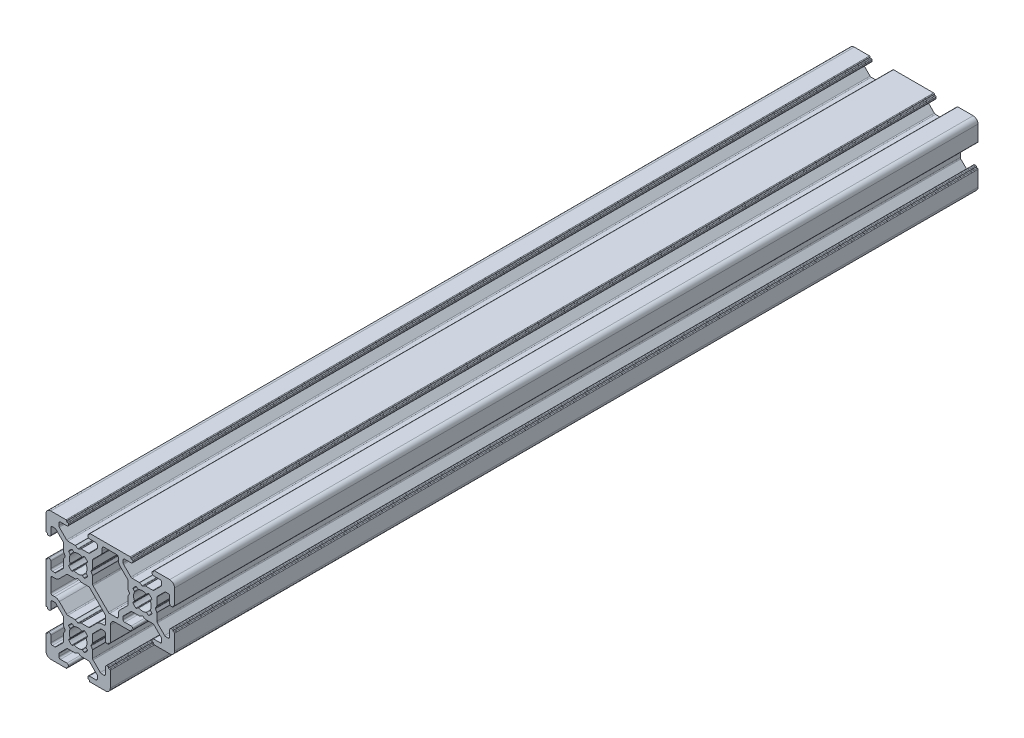
SolidWorks part; units mm, degrees
ref_plane "Front Plane" through (0, 0, 0) normal (0, 0, 1) x (1, 0, 0)
ref_plane "Top Plane" through (0, 0, 0) normal (0, 1, 0) x (1, 0, 0)
ref_plane "Right Plane" through (0, 0, 0) normal (1, 0, 0) x (0, 0, -1)
sketch "Sketch1" plane through (0, 0, 0) normal (0, 0, 1) x (1, 0, 0)
  line L0 (-3.2322, -4.5) -> (-0.9536, -4.5)
  line L1 (-0.8536, -4.4732) -> (-0.1, -4.0381)
  line L2 (0.1, -4.0381) -> (0.8536, -4.4732)
  line L3 (0.9536, -4.5) -> (3.2322, -4.5)
  line L4 (3.5858, -4.6464) -> (8.3536, -9.4142)
  line L5 (8.5, -12) -> (8.5, -9.7678)
  line L6 (-3.55, 9.7) -> (-3.55, 9.8)
  line L7 (-3.35, 9.5) -> (-3.2, 9.5)
  line L8 (-3, 9) -> (-3, 9.3)
  line L9 (-5.5, 8.5) -> (-3.5, 8.5)
  line L10 (-6, 7.2678) -> (-6, 8)
  line L12 (-3.2322, 4.5) -> (-0.9536, 4.5)
  line L13 (-0.8536, 4.4732) -> (-0.1, 4.0381)
  line L14 (0.1, 4.0381) -> (0.8536, 4.4732)
  line L15 (0.9536, 4.5) -> (3.2322, 4.5)
  line L16 (3.5858, 4.6464) -> (5.8536, 6.9142)
  line L17 (6, 7.2678) -> (6, 8)
  line L18 (5.5, 8.5) -> (3.5, 8.5)
  line L19 (3, 9) -> (3, 9.3)
  line L20 (3.2, 9.5) -> (3.3, 9.5)
  line L21 (3.5, 9.7) -> (3.5, 9.8)
  line L23 (3.7, 10) -> (16.2, 10)
  line L24 (16.4, 9.7) -> (16.4, 9.8)
  line L25 (16.6, 9.5) -> (16.8, 9.5)
  line L26 (17, 9) -> (17, 9.3)
  line L27 (14.5, 8.5) -> (16.5, 8.5)
  line L28 (14, 7.2678) -> (14, 8)
  line L29 (14.1464, 6.9142) -> (16.4142, 4.6464)
  line L30 (16.7678, 4.5) -> (19.0464, 4.5)
  line L31 (19.1464, 4.4732) -> (19.9, 4.0381)
  line L32 (20.1, 4.0381) -> (20.8536, 4.4732)
  line L33 (20.9536, 4.5) -> (23.2322, 4.5)
  line L34 (23.5858, 4.6464) -> (25.8536, 6.9142)
  line L35 (26, 7.2678) -> (26, 8)
  line L36 (25.5, 8.5) -> (23.5, 8.5)
  line L37 (23, 9) -> (23, 9.3)
  line L38 (23.2, 9.5) -> (23.3, 9.5)
  line L39 (23.5, 9.7) -> (23.5, 9.8)
  line L40 (23.7, 10) -> (28.5, 10)
  line L41 (30, 3.7) -> (30, 8.5)
  line L42 (29.7, 3.5) -> (29.8, 3.5)
  line L43 (29.5, 3.2) -> (29.5, 3.3)
  line L44 (29, 3) -> (29.3, 3)
  line L45 (28.5, 3.5) -> (28.5, 5.5)
  line L46 (27.2678, 6) -> (28, 6)
  line L47 (24.6464, 3.5858) -> (26.9142, 5.8536)
  line L48 (24.5, 0.9536) -> (24.5, 3.2322)
  line L49 (24.0381, 0.1) -> (24.4732, 0.8536)
  line L50 (24.0381, -0.1) -> (24.4732, -0.8536)
  line L51 (24.5, -3.2322) -> (24.5, -0.9536)
  line L52 (24.6464, -3.5858) -> (26.9142, -5.8536)
  line L53 (27.2678, -6) -> (28, -6)
  line L54 (28.5, -5.5) -> (28.5, -3.5)
  line L55 (29, -3) -> (29.3, -3)
  line L56 (29.5, -3.3) -> (29.5, -3.2)
  line L57 (29.7, -3.5) -> (29.8, -3.5)
  line L58 (30, -8.5) -> (30, -3.7)
  line L59 (23.7, -10) -> (28.5, -10)
  line L60 (23.5, -9.8) -> (23.5, -9.7)
  line L61 (23.2, -9.5) -> (23.3, -9.5)
  line L62 (23, -9.3) -> (23, -9)
  line L63 (23.5, -8.5) -> (25.5, -8.5)
  line L64 (26, -8) -> (26, -7.2678)
  line L65 (25.8536, -6.9142) -> (23.5858, -4.6464)
  line L66 (23.2322, -4.5) -> (20.9536, -4.5)
  line L67 (20.8536, -4.4732) -> (20.1, -4.0381)
  line L68 (19.1464, -4.4732) -> (19.9, -4.0381)
  line L69 (19.0464, -4.5) -> (16.7678, -4.5)
  line L70 (14.1464, -6.9142) -> (16.4142, -4.6464)
  line L71 (14, -8) -> (14, -7.2678)
  line L72 (14.5, -8.5) -> (16.5, -8.5)
  line L73 (17, -9.3) -> (17, -9)
  line L74 (16.65, -9.5) -> (16.8, -9.5)
  line L75 (16.45, -9.8) -> (16.45, -9.7)
  line L76 (11.5, -10) -> (16.25, -10)
  line L77 (10, -16.3) -> (10, -11.5)
  line L78 (9.8, -16.5) -> (9.7, -16.5)
  line L79 (9.5, -16.8) -> (9.5, -16.7)
  line L80 (9.3, -17) -> (9, -17)
  line L81 (8.5, -16.5) -> (8.5, -14.5)
  line L82 (7.2678, -14) -> (8, -14)
  line L83 (4.6464, -16.4142) -> (6.9142, -14.1464)
  line L84 (4.5, -19.0464) -> (4.5, -16.7678)
  line L85 (4.0381, -19.9) -> (4.4732, -19.1464)
  line L86 (4.0381, -20.1) -> (4.4732, -20.8536)
  line L87 (4.5, -23.2322) -> (4.5, -20.9536)
  line L88 (4.6464, -23.5858) -> (6.9142, -25.8536)
  line L89 (7.2678, -26) -> (8, -26)
  line L90 (8.5, -25.5) -> (8.5, -23.5)
  line L91 (9, -23) -> (9.3, -23)
  line L92 (9.5, -23.3) -> (9.5, -23.2)
  line L93 (9.7, -23.5) -> (9.8, -23.5)
  line L94 (10, -28.5) -> (10, -23.7)
  line L95 (8.5, -30) -> (3.7, -30)
  line L96 (3.5, -29.8) -> (3.5, -29.7)
  line L97 (3.3, -29.5) -> (3.2, -29.5)
  line L98 (3, -29.3) -> (3, -29)
  line L99 (3.5, -28.5) -> (5.5, -28.5)
  line L100 (6, -28) -> (6, -27.2678)
  line L101 (5.8536, -26.9142) -> (3.5858, -24.6464)
  line L102 (3.2322, -24.5) -> (0.9536, -24.5)
  line L103 (0.8536, -24.4732) -> (0.1, -24.0381)
  line L104 (-0.8536, -24.4732) -> (-0.1, -24.0381)
  line L105 (-0.9536, -24.5) -> (-3.2322, -24.5)
  line L106 (-5.8536, -26.9142) -> (-3.5858, -24.6464)
  line L107 (-6, -28) -> (-6, -27.2678)
  line L108 (-5.5, -28.5) -> (-3.5, -28.5)
  line L109 (-3, -29.3) -> (-3, -29)
  line L110 (-3.2, -29.5) -> (-3.3, -29.5)
  line L111 (-3.5, -29.8) -> (-3.5, -29.7)
  line L112 (-3.7, -30) -> (-8.5, -30)
  line L113 (-10, -28.5) -> (-10, -23.75)
  line L114 (-9.8, -23.55) -> (-9.7, -23.55)
  line L115 (-9.5, -23.35) -> (-9.5, -23.2)
  line L116 (-9.3, -23) -> (-9, -23)
  line L117 (-8.5, -23.5) -> (-8.5, -25.5)
  line L118 (-8, -26) -> (-7.2678, -26)
  line L119 (-6.9142, -25.8536) -> (-4.6464, -23.5858)
  line L120 (-4.5, -23.2322) -> (-4.5, -20.9536)
  line L121 (-4.4732, -20.8536) -> (-4.0381, -20.1)
  line L122 (-4.0381, -19.9) -> (-4.4732, -19.1464)
  line L123 (-4.5, -19.0464) -> (-4.5, -16.7678)
  line L124 (-4.6464, -16.4142) -> (-6.9142, -14.1464)
  line L125 (-7.2678, -14) -> (-8, -14)
  line L126 (-8.5, -16.5) -> (-8.5, -14.5)
  line L127 (-9, -17) -> (-9.3, -17)
  line L128 (-9.5, -16.8) -> (-9.5, -16.65)
  line L129 (-9.7, -16.45) -> (-9.8, -16.45)
  line L131 (2.5259, 1.3623) -> (2.8916, 1.8006)
  line L132 (1.3623, 2.5259) -> (1.8006, 2.8916)
  line L133 (-1.3623, 2.5259) -> (-1.8006, 2.8916)
  line L134 (-2.8912, 1.8002) -> (-2.5243, 1.3629)
  line L135 (-2.8912, -1.8002) -> (-2.5243, -1.3629)
  line L136 (-1.7927, -2.8965) -> (-1.3554, -2.5296)
  line L137 (1.3623, -2.5259) -> (1.8006, -2.8916)
  line L138 (2.8916, -1.8006) -> (2.5259, -1.3623)
  line L139 (3.2322, -15.5) -> (0.9536, -15.5)
  line L140 (-1.3623, -17.4741) -> (-1.8006, -17.1084)
  line L141 (-2.8916, -18.1994) -> (-2.5259, -18.6377)
  line L142 (-2.8916, -21.8006) -> (-2.5259, -21.3623)
  line L143 (-1.8006, -22.8916) -> (-1.3623, -22.5259)
  line L144 (1.3623, -22.5259) -> (1.8006, -22.8916)
  line L145 (2.8916, -21.8006) -> (2.5259, -21.3623)
  line L146 (2.5259, -18.6377) -> (2.8916, -18.1994)
  line L147 (1.3623, -17.4741) -> (1.8006, -17.1084)
  line L148 (-8.5, -12) -> (-8.5, -8)
  line L149 (-7.2678, -12.5) -> (-8, -12.5)
  line L150 (-0.9536, -15.5) -> (-3.2322, -15.5)
  line L151 (-3.5858, -15.3536) -> (-5.8536, -13.0858)
  line L152 (0.8536, -15.5268) -> (0.1, -15.9619)
  line L153 (-0.1, -15.9619) -> (-0.8536, -15.5268)
  line L154 (-9.8, 3.55) -> (-9.7, 3.55)
  line L155 (-9.5, 3.2) -> (-9.5, 3.35)
  line L156 (-9.3, 3) -> (-9, 3)
  line L157 (-8.5, 3.5) -> (-8.5, 5.5)
  line L158 (-8, 6) -> (-7.2678, 6)
  line L159 (-6.9142, 5.8536) -> (-4.6464, 3.5858)
  line L160 (-4.5, 0.9536) -> (-4.5, 3.2322)
  line L161 (-4.4732, 0.8536) -> (-4.0381, 0.1)
  line L162 (-4.4732, -0.8536) -> (-4.0381, -0.1)
  line L163 (-4.5, -3.2322) -> (-4.5, -0.9536)
  line L164 (-6.9142, -5.8536) -> (-4.6464, -3.5858)
  line L165 (-7.2678, -6) -> (-8, -6)
  line L166 (-8.5, -5.5) -> (-8.5, -3.5)
  line L167 (-9, -3) -> (-9.3, -3)
  line L168 (-9.5, -3.35) -> (-9.5, -3.2)
  line L169 (-9.7, -3.55) -> (-9.8, -3.55)
  line L170 (-10, 3.75) -> (-10, 8.5)
  line L171 (-8.5, 10) -> (-3.75, 10)
  line L172 (-10, -16.25) -> (-10, -3.75)
  line L173 (-7.2678, -7.5) -> (-8, -7.5)
  line L174 (-3.5858, -4.6464) -> (-5.8536, -6.9142)
  line L175 (-3.5858, 4.6464) -> (-5.8536, 6.9142)
  line L176 (5.8536, -13.0858) -> (3.5858, -15.3536)
  line L177 (7.2678, -12.5) -> (8, -12.5)
  line L178 (17.4688, 1.3572) -> (17.1088, 1.8002)
  line L179 (18.1998, 2.8912) -> (18.6428, 2.5312)
  line L180 (21.3554, 2.5296) -> (21.7983, 2.8897)
  line L181 (22.5296, 1.3554) -> (22.8897, 1.7983)
  line L182 (22.5296, -1.3554) -> (22.8897, -1.7983)
  line L183 (21.7983, -2.8897) -> (21.3554, -2.5296)
  line L184 (18.1998, -2.8912) -> (18.6428, -2.5312)
  line L185 (17.1088, -1.8002) -> (17.4688, -1.3572)
  line L186 (12, -8.5) -> (9.7678, -8.5)
  line L187 (12, 8.5) -> (8, 8.5)
  line L188 (4.0381, 0.1) -> (4.4732, 0.8536)
  line L189 (9.4142, -8.3536) -> (4.6464, -3.5858)
  line L190 (4.5, -3.2322) -> (4.5, -0.9536)
  line L191 (4.4732, -0.8536) -> (4.0381, -0.1)
  line L192 (4.6464, 3.5858) -> (6.9142, 5.8536)
  line L193 (4.5, 0.9536) -> (4.5, 3.2322)
  line L194 (7.5, 7.2678) -> (7.5, 8)
  line L195 (15.9619, 0.1) -> (15.5268, 0.8536)
  line L196 (15.5268, -0.8536) -> (15.9619, -0.1)
  line L197 (13.0858, -5.8536) -> (15.3536, -3.5858)
  line L198 (12.5, -7.2678) -> (12.5, -8)
  line L199 (15.5, -3.2322) -> (15.5, -0.9536)
  line L200 (15.3536, 3.5858) -> (13.0858, 5.8536)
  line L201 (15.5, 0.9536) -> (15.5, 3.2322)
  line L202 (12.5, 7.2678) -> (12.5, 8)
  line L203 (0, 11.9931) -> (0, -30.4658) construction
  line L204 (-13.2913, 0) -> (29.7, 0) construction
  line L205 (20, 11.9931) -> (20, -22.0156) construction
  line L206 (-15.5823, -20) -> (12, -20) construction
  line L207 (10, 11.9931) -> (10, -32.444) construction
  line L208 (-14.6648, -10) -> (36.8031, -10) construction
  arc A0 (-0.9536, -4.5) -> (-0.8536, -4.4732) centre (-0.9536, -4.3) ccw
  arc A1 (0.1, -4.0381) -> (-0.1, -4.0381) centre (0, -4.2113) ccw
  arc A2 (0.8536, -4.4732) -> (0.9536, -4.5) centre (0.9536, -4.3) ccw
  arc A3 (3.5858, -4.6464) -> (3.2322, -4.5) centre (3.2322, -5) ccw
  arc A4 (8.5, -9.7678) -> (8.3536, -9.4142) centre (8, -9.7678) ccw
  arc A5 (-3.55, 9.8) -> (-3.75, 10) centre (-3.75, 9.8) ccw
  arc A6 (-3.55, 9.7) -> (-3.35, 9.5) centre (-3.35, 9.7) ccw
  arc A7 (-3, 9.3) -> (-3.2, 9.5) centre (-3.2, 9.3) ccw
  arc A8 (-3.5, 8.5) -> (-3, 9) centre (-3.5, 9) ccw
  arc A9 (-5.5, 8.5) -> (-6, 8) centre (-5.5, 8) ccw
  arc A10 (-6, 7.2678) -> (-5.8536, 6.9142) centre (-5.5, 7.2678) ccw
  arc A11 (-3.5858, 4.6464) -> (-3.2322, 4.5) centre (-3.2322, 5) ccw
  arc A12 (-0.8536, 4.4732) -> (-0.9536, 4.5) centre (-0.9536, 4.3) ccw
  arc A13 (-0.1, 4.0381) -> (0.1, 4.0381) centre (0, 4.2113) ccw
  arc A14 (0.9536, 4.5) -> (0.8536, 4.4732) centre (0.9536, 4.3) ccw
  arc A15 (3.2322, 4.5) -> (3.5858, 4.6464) centre (3.2322, 5) ccw
  arc A16 (5.8536, 6.9142) -> (6, 7.2678) centre (5.5, 7.2678) ccw
  arc A17 (6, 8) -> (5.5, 8.5) centre (5.5, 8) ccw
  arc A18 (3, 9) -> (3.5, 8.5) centre (3.5, 9) ccw
  arc A19 (3.2, 9.5) -> (3, 9.3) centre (3.2, 9.3) ccw
  arc A20 (3.3, 9.5) -> (3.5, 9.7) centre (3.3, 9.7) ccw
  arc A21 (3.7, 10) -> (3.5, 9.8) centre (3.7, 9.8) ccw
  arc A22 (16.4, 9.8) -> (16.2, 10) centre (16.2, 9.8) ccw
  arc A23 (16.4, 9.7) -> (16.6, 9.5) centre (16.6, 9.7) ccw
  arc A24 (17, 9.3) -> (16.8, 9.5) centre (16.8, 9.3) ccw
  arc A25 (16.5, 8.5) -> (17, 9) centre (16.5, 9) ccw
  arc A26 (14.5, 8.5) -> (14, 8) centre (14.5, 8) ccw
  arc A27 (14, 7.2678) -> (14.1464, 6.9142) centre (14.5, 7.2678) ccw
  arc A28 (16.4142, 4.6464) -> (16.7678, 4.5) centre (16.7678, 5) ccw
  arc A29 (19.1464, 4.4732) -> (19.0464, 4.5) centre (19.0464, 4.3) ccw
  arc A30 (19.9, 4.0381) -> (20.1, 4.0381) centre (20, 4.2113) ccw
  arc A31 (20.9536, 4.5) -> (20.8536, 4.4732) centre (20.9536, 4.3) ccw
  arc A32 (23.2322, 4.5) -> (23.5858, 4.6464) centre (23.2322, 5) ccw
  arc A33 (25.8536, 6.9142) -> (26, 7.2678) centre (25.5, 7.2678) ccw
  arc A34 (26, 8) -> (25.5, 8.5) centre (25.5, 8) ccw
  arc A35 (23, 9) -> (23.5, 8.5) centre (23.5, 9) ccw
  arc A36 (23.2, 9.5) -> (23, 9.3) centre (23.2, 9.3) ccw
  arc A37 (23.3, 9.5) -> (23.5, 9.7) centre (23.3, 9.7) ccw
  arc A38 (23.7, 10) -> (23.5, 9.8) centre (23.7, 9.8) ccw
  arc A39 (30, 8.5) -> (28.5, 10) centre (28.5, 8.5) ccw
  arc A40 (29.8, 3.5) -> (30, 3.7) centre (29.8, 3.7) ccw
  arc A41 (29.7, 3.5) -> (29.5, 3.3) centre (29.7, 3.3) ccw
  arc A42 (29.3, 3) -> (29.5, 3.2) centre (29.3, 3.2) ccw
  arc A43 (28.5, 3.5) -> (29, 3) centre (29, 3.5) ccw
  arc A44 (28.5, 5.5) -> (28, 6) centre (28, 5.5) ccw
  arc A45 (27.2678, 6) -> (26.9142, 5.8536) centre (27.2678, 5.5) ccw
  arc A46 (24.6464, 3.5858) -> (24.5, 3.2322) centre (25, 3.2322) ccw
  arc A47 (24.4732, 0.8536) -> (24.5, 0.9536) centre (24.3, 0.9536) ccw
  arc A48 (24.0381, 0.1) -> (24.0381, -0.1) centre (24.2113, 0) ccw
  arc A49 (24.5, -0.9536) -> (24.4732, -0.8536) centre (24.3, -0.9536) ccw
  arc A50 (24.5, -3.2322) -> (24.6464, -3.5858) centre (25, -3.2322) ccw
  arc A51 (26.9142, -5.8536) -> (27.2678, -6) centre (27.2678, -5.5) ccw
  arc A52 (28, -6) -> (28.5, -5.5) centre (28, -5.5) ccw
  arc A53 (29, -3) -> (28.5, -3.5) centre (29, -3.5) ccw
  arc A54 (29.5, -3.2) -> (29.3, -3) centre (29.3, -3.2) ccw
  arc A55 (29.5, -3.3) -> (29.7, -3.5) centre (29.7, -3.3) ccw
  arc A56 (30, -3.7) -> (29.8, -3.5) centre (29.8, -3.7) ccw
  arc A57 (28.5, -10) -> (30, -8.5) centre (28.5, -8.5) ccw
  arc A58 (23.5, -9.8) -> (23.7, -10) centre (23.7, -9.8) ccw
  arc A59 (23.5, -9.7) -> (23.3, -9.5) centre (23.3, -9.7) ccw
  arc A60 (23, -9.3) -> (23.2, -9.5) centre (23.2, -9.3) ccw
  arc A61 (23.5, -8.5) -> (23, -9) centre (23.5, -9) ccw
  arc A62 (25.5, -8.5) -> (26, -8) centre (25.5, -8) ccw
  arc A63 (26, -7.2678) -> (25.8536, -6.9142) centre (25.5, -7.2678) ccw
  arc A64 (23.5858, -4.6464) -> (23.2322, -4.5) centre (23.2322, -5) ccw
  arc A65 (20.8536, -4.4732) -> (20.9536, -4.5) centre (20.9536, -4.3) ccw
  arc A66 (20.1, -4.0381) -> (19.9, -4.0381) centre (20, -4.2113) ccw
  arc A67 (19.0464, -4.5) -> (19.1464, -4.4732) centre (19.0464, -4.3) ccw
  arc A68 (16.7678, -4.5) -> (16.4142, -4.6464) centre (16.7678, -5) ccw
  arc A69 (14.1464, -6.9142) -> (14, -7.2678) centre (14.5, -7.2678) ccw
  arc A70 (14, -8) -> (14.5, -8.5) centre (14.5, -8) ccw
  arc A71 (17, -9) -> (16.5, -8.5) centre (16.5, -9) ccw
  arc A72 (16.8, -9.5) -> (17, -9.3) centre (16.8, -9.3) ccw
  arc A73 (16.65, -9.5) -> (16.45, -9.7) centre (16.65, -9.7) ccw
  arc A74 (16.25, -10) -> (16.45, -9.8) centre (16.25, -9.8) ccw
  arc A75 (11.5, -10) -> (10, -11.5) centre (11.5, -11.5) ccw
  arc A76 (9.8, -16.5) -> (10, -16.3) centre (9.8, -16.3) ccw
  arc A77 (9.7, -16.5) -> (9.5, -16.7) centre (9.7, -16.7) ccw
  arc A78 (9.3, -17) -> (9.5, -16.8) centre (9.3, -16.8) ccw
  arc A79 (8.5, -16.5) -> (9, -17) centre (9, -16.5) ccw
  arc A80 (8.5, -14.5) -> (8, -14) centre (8, -14.5) ccw
  arc A81 (7.2678, -14) -> (6.9142, -14.1464) centre (7.2678, -14.5) ccw
  arc A82 (4.6464, -16.4142) -> (4.5, -16.7678) centre (5, -16.7678) ccw
  arc A83 (4.4732, -19.1464) -> (4.5, -19.0464) centre (4.3, -19.0464) ccw
  arc A84 (4.0381, -19.9) -> (4.0381, -20.1) centre (4.2113, -20) ccw
  arc A85 (4.5, -20.9536) -> (4.4732, -20.8536) centre (4.3, -20.9536) ccw
  arc A86 (4.5, -23.2322) -> (4.6464, -23.5858) centre (5, -23.2322) ccw
  arc A87 (6.9142, -25.8536) -> (7.2678, -26) centre (7.2678, -25.5) ccw
  arc A88 (8, -26) -> (8.5, -25.5) centre (8, -25.5) ccw
  arc A89 (9, -23) -> (8.5, -23.5) centre (9, -23.5) ccw
  arc A90 (9.5, -23.2) -> (9.3, -23) centre (9.3, -23.2) ccw
  arc A91 (9.5, -23.3) -> (9.7, -23.5) centre (9.7, -23.3) ccw
  arc A92 (10, -23.7) -> (9.8, -23.5) centre (9.8, -23.7) ccw
  arc A93 (8.5, -30) -> (10, -28.5) centre (8.5, -28.5) ccw
  arc A94 (3.5, -29.8) -> (3.7, -30) centre (3.7, -29.8) ccw
  arc A95 (3.5, -29.7) -> (3.3, -29.5) centre (3.3, -29.7) ccw
  arc A96 (3, -29.3) -> (3.2, -29.5) centre (3.2, -29.3) ccw
  arc A97 (3.5, -28.5) -> (3, -29) centre (3.5, -29) ccw
  arc A98 (5.5, -28.5) -> (6, -28) centre (5.5, -28) ccw
  arc A99 (6, -27.2678) -> (5.8536, -26.9142) centre (5.5, -27.2678) ccw
  arc A100 (3.5858, -24.6464) -> (3.2322, -24.5) centre (3.2322, -25) ccw
  arc A101 (0.8536, -24.4732) -> (0.9536, -24.5) centre (0.9536, -24.3) ccw
  arc A102 (0.1, -24.0381) -> (-0.1, -24.0381) centre (0, -24.2113) ccw
  arc A103 (-0.9536, -24.5) -> (-0.8536, -24.4732) centre (-0.9536, -24.3) ccw
  arc A104 (-3.2322, -24.5) -> (-3.5858, -24.6464) centre (-3.2322, -25) ccw
  arc A105 (-5.8536, -26.9142) -> (-6, -27.2678) centre (-5.5, -27.2678) ccw
  arc A106 (-6, -28) -> (-5.5, -28.5) centre (-5.5, -28) ccw
  arc A107 (-3, -29) -> (-3.5, -28.5) centre (-3.5, -29) ccw
  arc A108 (-3.2, -29.5) -> (-3, -29.3) centre (-3.2, -29.3) ccw
  arc A109 (-3.3, -29.5) -> (-3.5, -29.7) centre (-3.3, -29.7) ccw
  arc A110 (-3.7, -30) -> (-3.5, -29.8) centre (-3.7, -29.8) ccw
  arc A111 (-10, -28.5) -> (-8.5, -30) centre (-8.5, -28.5) ccw
  arc A112 (-9.8, -23.55) -> (-10, -23.75) centre (-9.8, -23.75) ccw
  arc A113 (-9.7, -23.55) -> (-9.5, -23.35) centre (-9.7, -23.35) ccw
  arc A114 (-9.3, -23) -> (-9.5, -23.2) centre (-9.3, -23.2) ccw
  arc A115 (-8.5, -23.5) -> (-9, -23) centre (-9, -23.5) ccw
  arc A116 (-8.5, -25.5) -> (-8, -26) centre (-8, -25.5) ccw
  arc A117 (-7.2678, -26) -> (-6.9142, -25.8536) centre (-7.2678, -25.5) ccw
  arc A118 (-4.6464, -23.5858) -> (-4.5, -23.2322) centre (-5, -23.2322) ccw
  arc A119 (-4.4732, -20.8536) -> (-4.5, -20.9536) centre (-4.3, -20.9536) ccw
  arc A120 (-4.0381, -20.1) -> (-4.0381, -19.9) centre (-4.2113, -20) ccw
  arc A121 (-4.5, -19.0464) -> (-4.4732, -19.1464) centre (-4.3, -19.0464) ccw
  arc A122 (-4.5, -16.7678) -> (-4.6464, -16.4142) centre (-5, -16.7678) ccw
  arc A123 (-6.9142, -14.1464) -> (-7.2678, -14) centre (-7.2678, -14.5) ccw
  arc A124 (-8, -14) -> (-8.5, -14.5) centre (-8, -14.5) ccw
  arc A125 (-9, -17) -> (-8.5, -16.5) centre (-9, -16.5) ccw
  arc A126 (-9.5, -16.8) -> (-9.3, -17) centre (-9.3, -16.8) ccw
  arc A127 (-9.5, -16.65) -> (-9.7, -16.45) centre (-9.7, -16.65) ccw
  arc A128 (-10, -16.25) -> (-9.8, -16.45) centre (-9.8, -16.25) ccw
  arc A129 (2.75, 0) -> (2.4978, 1.1505) centre (0, 0) ccw
  arc A130 (2.5259, 1.3623) -> (2.4978, 1.1505) centre (2.6794, 1.2342) ccw
  arc A131 (2.8916, 1.8006) -> (2.9015, 2.0439) centre (2.738, 1.9287) ccw
  arc A132 (2.9015, 2.0439) -> (2.0439, 2.9015) centre (0, 0) ccw
  arc A133 (2.0439, 2.9015) -> (1.8006, 2.8916) centre (1.9287, 2.738) ccw
  arc A134 (1.1505, 2.4978) -> (1.3623, 2.5259) centre (1.2342, 2.6794) ccw
  arc A135 (1.1505, 2.4978) -> (-1.1505, 2.4978) centre (0, 0) ccw
  arc A136 (-1.3623, 2.5259) -> (-1.1505, 2.4978) centre (-1.2342, 2.6794) ccw
  arc A137 (-1.8006, 2.8916) -> (-2.0439, 2.9015) centre (-1.9287, 2.738) ccw
  arc A138 (-2.0439, 2.9015) -> (-2.9015, 2.0439) centre (0, 0) ccw
  arc A139 (-2.9015, 2.0439) -> (-2.8912, 1.8002) centre (-2.738, 1.9287) ccw
  arc A140 (-2.4869, 1.1738) -> (-2.5243, 1.3629) centre (-2.6775, 1.2343) ccw
  arc A141 (-2.4869, 1.1738) -> (-2.4971, -1.152) centre (0, 0) ccw
  arc A142 (-2.5243, -1.3629) -> (-2.4971, -1.152) centre (-2.6787, -1.2357) ccw
  arc A143 (-2.8912, -1.8002) -> (-2.9015, -2.0439) centre (-2.738, -1.9287) ccw
  arc A144 (-2.9015, -2.0439) -> (-2.0359, -2.9071) centre (0, 0) ccw
  arc A145 (-2.0359, -2.9071) -> (-1.7927, -2.8965) centre (-1.9212, -2.7433) ccw
  arc A146 (-1.1436, -2.5009) -> (-1.3554, -2.5296) centre (-1.2268, -2.6828) ccw
  arc A147 (-1.1436, -2.5009) -> (1.1505, -2.4978) centre (0, 0) ccw
  arc A148 (1.3623, -2.5259) -> (1.1505, -2.4978) centre (1.2342, -2.6794) ccw
  arc A149 (1.8006, -2.8916) -> (2.0439, -2.9015) centre (1.9287, -2.738) ccw
  arc A150 (2.0439, -2.9015) -> (2.9015, -2.0439) centre (0, 0) ccw
  arc A151 (2.9015, -2.0439) -> (2.8916, -1.8006) centre (2.738, -1.9287) ccw
  arc A152 (2.4978, -1.1505) -> (2.5259, -1.3623) centre (2.6794, -1.2342) ccw
  arc A153 (2.4978, -1.1505) -> (2.75, 0) centre (0, 0) ccw
  arc A154 (0, -17.25) -> (-1.1505, -17.5022) centre (0, -20) ccw
  arc A155 (-1.3623, -17.4741) -> (-1.1505, -17.5022) centre (-1.2342, -17.3206) ccw
  arc A156 (-1.8006, -17.1084) -> (-2.0439, -17.0985) centre (-1.9287, -17.262) ccw
  arc A157 (-2.0439, -17.0985) -> (-2.9015, -17.9561) centre (0, -20) ccw
  arc A158 (-2.9015, -17.9561) -> (-2.8916, -18.1994) centre (-2.738, -18.0713) ccw
  arc A159 (-2.4978, -18.8495) -> (-2.5259, -18.6377) centre (-2.6794, -18.7658) ccw
  arc A160 (-2.4978, -18.8495) -> (-2.4978, -21.1505) centre (0, -20) ccw
  arc A161 (-2.5259, -21.3623) -> (-2.4978, -21.1505) centre (-2.6794, -21.2342) ccw
  arc A162 (-2.8916, -21.8006) -> (-2.9015, -22.0439) centre (-2.738, -21.9287) ccw
  arc A163 (-2.9015, -22.0439) -> (-2.0439, -22.9015) centre (0, -20) ccw
  arc A164 (-2.0439, -22.9015) -> (-1.8006, -22.8916) centre (-1.9287, -22.738) ccw
  arc A165 (-1.1505, -22.4978) -> (-1.3623, -22.5259) centre (-1.2342, -22.6794) ccw
  arc A166 (-1.1505, -22.4978) -> (1.1505, -22.4978) centre (0, -20) ccw
  arc A167 (1.3623, -22.5259) -> (1.1505, -22.4978) centre (1.2342, -22.6794) ccw
  arc A168 (1.8006, -22.8916) -> (2.0439, -22.9015) centre (1.9287, -22.738) ccw
  arc A169 (2.0439, -22.9015) -> (2.9015, -22.0439) centre (0, -20) ccw
  arc A170 (2.9015, -22.0439) -> (2.8916, -21.8006) centre (2.738, -21.9287) ccw
  arc A171 (2.4978, -21.1505) -> (2.5259, -21.3623) centre (2.6794, -21.2342) ccw
  arc A172 (2.4978, -21.1505) -> (2.4978, -18.8495) centre (0, -20) ccw
  arc A173 (2.5259, -18.6377) -> (2.4978, -18.8495) centre (2.6794, -18.7658) ccw
  arc A174 (2.8916, -18.1994) -> (2.9015, -17.9561) centre (2.738, -18.0713) ccw
  arc A175 (2.9015, -17.9561) -> (2.0439, -17.0985) centre (0, -20) ccw
  arc A176 (2.0439, -17.0985) -> (1.8006, -17.1084) centre (1.9287, -17.262) ccw
  arc A177 (1.1505, -17.5022) -> (1.3623, -17.4741) centre (1.2342, -17.3206) ccw
  arc A178 (1.1505, -17.5022) -> (0, -17.25) centre (0, -20) ccw
  arc A179 (-5.8536, -13.0858) -> (-7.2678, -12.5) centre (-7.2678, -14.5) ccw
  arc A180 (-8.5, -12) -> (-8, -12.5) centre (-8, -12) ccw
  arc A181 (-3.5858, -15.3536) -> (-3.2322, -15.5) centre (-3.2322, -15) ccw
  arc A182 (-0.8536, -15.5268) -> (-0.9536, -15.5) centre (-0.9536, -15.7) ccw
  arc A183 (-0.1, -15.9619) -> (0.1, -15.9619) centre (0, -15.7887) ccw
  arc A184 (0.9536, -15.5) -> (0.8536, -15.5268) centre (0.9536, -15.7) ccw
  arc A185 (-10, 3.75) -> (-9.8, 3.55) centre (-9.8, 3.75) ccw
  arc A186 (-9.5, 3.35) -> (-9.7, 3.55) centre (-9.7, 3.35) ccw
  arc A187 (-9.5, 3.2) -> (-9.3, 3) centre (-9.3, 3.2) ccw
  arc A188 (-9, 3) -> (-8.5, 3.5) centre (-9, 3.5) ccw
  arc A189 (-8, 6) -> (-8.5, 5.5) centre (-8, 5.5) ccw
  arc A190 (-6.9142, 5.8536) -> (-7.2678, 6) centre (-7.2678, 5.5) ccw
  arc A191 (-4.5, 3.2322) -> (-4.6464, 3.5858) centre (-5, 3.2322) ccw
  arc A192 (-4.5, 0.9536) -> (-4.4732, 0.8536) centre (-4.3, 0.9536) ccw
  arc A193 (-4.0381, -0.1) -> (-4.0381, 0.1) centre (-4.2113, 0) ccw
  arc A194 (-4.4732, -0.8536) -> (-4.5, -0.9536) centre (-4.3, -0.9536) ccw
  arc A195 (-4.6464, -3.5858) -> (-4.5, -3.2322) centre (-5, -3.2322) ccw
  arc A196 (-7.2678, -6) -> (-6.9142, -5.8536) centre (-7.2678, -5.5) ccw
  arc A197 (-8.5, -5.5) -> (-8, -6) centre (-8, -5.5) ccw
  arc A198 (-8.5, -3.5) -> (-9, -3) centre (-9, -3.5) ccw
  arc A199 (-9.3, -3) -> (-9.5, -3.2) centre (-9.3, -3.2) ccw
  arc A200 (-9.7, -3.55) -> (-9.5, -3.35) centre (-9.7, -3.35) ccw
  arc A201 (-9.8, -3.55) -> (-10, -3.75) centre (-9.8, -3.75) ccw
  arc A202 (-8.5, 10) -> (-10, 8.5) centre (-8.5, 8.5) ccw
  arc A203 (-7.2678, -7.5) -> (-5.8536, -6.9142) centre (-7.2678, -5.5) ccw
  arc A204 (-8, -7.5) -> (-8.5, -8) centre (-8, -8) ccw
  arc A205 (-3.2322, -4.5) -> (-3.5858, -4.6464) centre (-3.2322, -5) ccw
  arc A206 (7.2678, -12.5) -> (5.8536, -13.0858) centre (7.2678, -14.5) ccw
  arc A207 (3.2322, -15.5) -> (3.5858, -15.3536) centre (3.2322, -15) ccw
  arc A208 (8, -12.5) -> (8.5, -12) centre (8, -12) ccw
  arc A209 (17.4991, 1.1436) -> (17.25, 0) centre (20, 0) ccw
  arc A210 (17.4991, 1.1436) -> (17.4688, 1.3572) centre (17.3172, 1.2268) ccw
  arc A211 (17.0985, 2.0439) -> (17.1088, 1.8002) centre (17.262, 1.9287) ccw
  arc A212 (17.9561, 2.9015) -> (17.0985, 2.0439) centre (20, 0) ccw
  arc A213 (18.1998, 2.8912) -> (17.9561, 2.9015) centre (18.0713, 2.738) ccw
  arc A214 (18.6428, 2.5312) -> (18.8564, 2.5009) centre (18.7732, 2.6828) ccw
  arc A215 (20, 2.75) -> (18.8564, 2.5009) centre (20, 0) ccw
  arc A216 (21.1436, 2.5009) -> (20, 2.75) centre (20, 0) ccw
  arc A217 (21.1436, 2.5009) -> (21.3554, 2.5296) centre (21.2268, 2.6828) ccw
  arc A218 (22.0439, 2.9015) -> (21.7983, 2.8897) centre (21.9287, 2.738) ccw
  arc A219 (22.9015, 2.0439) -> (22.0439, 2.9015) centre (20, 0) ccw
  arc A220 (22.8897, 1.7983) -> (22.9015, 2.0439) centre (22.738, 1.9287) ccw
  arc A221 (22.5296, 1.3554) -> (22.5009, 1.1436) centre (22.6828, 1.2268) ccw
  arc A222 (22.75, 0) -> (22.5009, 1.1436) centre (20, 0) ccw
  arc A223 (22.5009, -1.1436) -> (22.75, 0) centre (20, 0) ccw
  arc A224 (22.5009, -1.1436) -> (22.5296, -1.3554) centre (22.6828, -1.2268) ccw
  arc A225 (22.9015, -2.0439) -> (22.8897, -1.7983) centre (22.738, -1.9287) ccw
  arc A226 (22.0439, -2.9015) -> (22.9015, -2.0439) centre (20, 0) ccw
  arc A227 (21.7983, -2.8897) -> (22.0439, -2.9015) centre (21.9287, -2.738) ccw
  arc A228 (21.3554, -2.5296) -> (21.1436, -2.5009) centre (21.2268, -2.6828) ccw
  arc A229 (20, -2.75) -> (21.1436, -2.5009) centre (20, 0) ccw
  arc A230 (18.8564, -2.5009) -> (20, -2.75) centre (20, 0) ccw
  arc A231 (18.8564, -2.5009) -> (18.6428, -2.5312) centre (18.7732, -2.6828) ccw
  arc A232 (17.9561, -2.9015) -> (18.1998, -2.8912) centre (18.0713, -2.738) ccw
  arc A233 (17.0985, -2.0439) -> (17.9561, -2.9015) centre (20, 0) ccw
  arc A234 (17.1088, -1.8002) -> (17.0985, -2.0439) centre (17.262, -1.9287) ccw
  arc A235 (17.4688, -1.3572) -> (17.4991, -1.1436) centre (17.3172, -1.2268) ccw
  arc A236 (17.25, 0) -> (17.4991, -1.1436) centre (20, 0) ccw
  arc A237 (4.0381, 0.1) -> (4.0381, -0.1) centre (4.2113, 0) ccw
  arc A238 (4.5, -3.2322) -> (4.6464, -3.5858) centre (5, -3.2322) ccw
  arc A239 (4.5, -0.9536) -> (4.4732, -0.8536) centre (4.3, -0.9536) ccw
  arc A240 (9.4142, -8.3536) -> (9.7678, -8.5) centre (9.7678, -8) ccw
  arc A241 (6.9142, 5.8536) -> (7.5, 7.2678) centre (5.5, 7.2678) ccw
  arc A242 (4.6464, 3.5858) -> (4.5, 3.2322) centre (5, 3.2322) ccw
  arc A243 (3.0003, 4.5) -> (3, 4.5) centre (3, 3) ccw
  arc A244 (4.4732, 0.8536) -> (4.5, 0.9536) centre (4.3, 0.9536) ccw
  arc A245 (8, 8.5) -> (7.5, 8) centre (8, 8) ccw
  arc A246 (12, -8.5) -> (12.5, -8) centre (12, -8) ccw
  arc A247 (13.0858, -5.8536) -> (12.5, -7.2678) centre (14.5, -7.2678) ccw
  arc A248 (15.3536, -3.5858) -> (15.5, -3.2322) centre (15, -3.2322) ccw
  arc A249 (15.5268, -0.8536) -> (15.5, -0.9536) centre (15.7, -0.9536) ccw
  arc A250 (15.9619, -0.1) -> (15.9619, 0.1) centre (15.7887, 0) ccw
  arc A251 (12.5, 7.2678) -> (13.0858, 5.8536) centre (14.5, 7.2678) ccw
  arc A252 (15.5, 0.9536) -> (15.5268, 0.8536) centre (15.7, 0.9536) ccw
  arc A253 (15.5, 3.2322) -> (15.3536, 3.5858) centre (15, 3.2322) ccw
  arc A254 (12.5, 8) -> (12, 8.5) centre (12, 8) ccw
  dimension "D5" = 5.5
  dimension "D1" = 20
  dimension "D2" = 20
  dimension "D3" = 10
  dimension "D4" = 10
  dimension "D6" = 6
  dimension "D7" = 20
  dimension "D8" = 40
  dimension "D9" = 20
  dimension "D10" = 40
  dimension "D11" = 6
  dimension "D12" = 6
  dimension "D13" = 6
extrude "Extrude1" add sketch "Sketch1" along normal blind 250 contours L171 A202 L170 A185 L154 A186 L155 A187 L156 A188 L157 A189 L158 A190 L159 A191 L160 A192 L161 A193 L162 A194 L163 A195 L164 A196 L165 A197 L166 A198 L167 A199 L168 A200 L169 A201 L172 A128 L129 A127 L128 A126 L127 A125 L126 A124 L125 A123 L124 A122 L123
